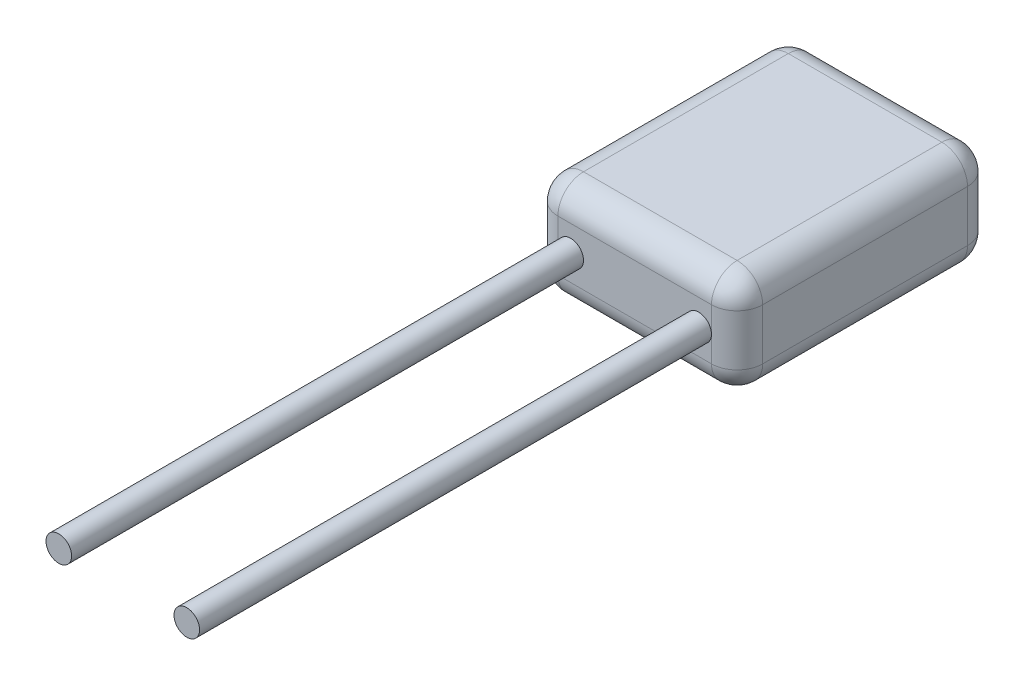
SolidWorks part; units mm, degrees
ref_plane "Front Plane" through (0, 0, 0) normal (0, 0, 1) x (1, 0, 0)
ref_plane "Top Plane" through (0, 0, 0) normal (0, 1, 0) x (1, 0, 0)
ref_plane "Right Plane" through (0, 0, 0) normal (1, 0, 0) x (0, 0, -1)
sketch "Sketch1" plane through (0, 0, 0) normal (0, 0, 1) x (1, 0, 0)
  line L1 (-2, -1) -> (2, -1)
  line L2 (-2, -1) -> (-2, 1)
  line L3 (-2, 1) -> (2, 1)
  line L4 (2, -1) -> (2, 1)
  line L5 (-2, -1) -> (2, 1) construction
  line L6 (-2, 1) -> (2, -1) construction
  point P0 (0, 0)
  dimension "D1" = 4
  dimension "D2" = 2
extrude "Boss-Extrude1" add sketch "Sketch1" along normal blind 5
sketch "Sketch2" plane through (0, 0, 5) normal (0, 0, 1) x (1, 0, 0)
  line L0 (0, 1) -> (0, -1) construction
  line L1 (2, 1) -> (-2, 1) construction
  line L2 (-1.25, 0) -> (1.25, 0) construction
  line L4 (2, -1) -> (2, 1)
  line L5 (2, 1) -> (-2, 1)
  line L6 (-2, 1) -> (-2, -1)
  line L7 (-2, -1) -> (2, -1)
  line L8 (2, -1) -> (2, 1)
  line L9 (2, 1) -> (-2, 1)
  line L10 (-2, 1) -> (-2, -1)
  line L11 (-2, -1) -> (2, -1)
  circle A0 centre (-1.25, 0) radius 0.25
  circle A1 centre (1.25, 0) radius 0.25
  point P15 (0, 0)
  dimension "D2" = 0.5
  dimension "D3" = 1.25
  dimension "D1" = 0
extrude "Boss-Extrude2" add sketch "Sketch2" along normal blind 10 contours A0 | A1 region at (-1.25, 0, 5) region at (1.25, 0, 5)
fillet "Fillet1" radius 0.5 12 edges at (-2, -1, 2.5) (0, -1, 5) (2, -1, 2.5) (2, 1, 2.5) (0, 1, 5) (-2, 1, 2.5) (0, 1, 0) (0, -1, 0) (2, 0, 5) (-2, 0, 5) (-2, 0, 0) (2, 0, 0)
equation "\"D3@Sketch2\"=2.5/2"
